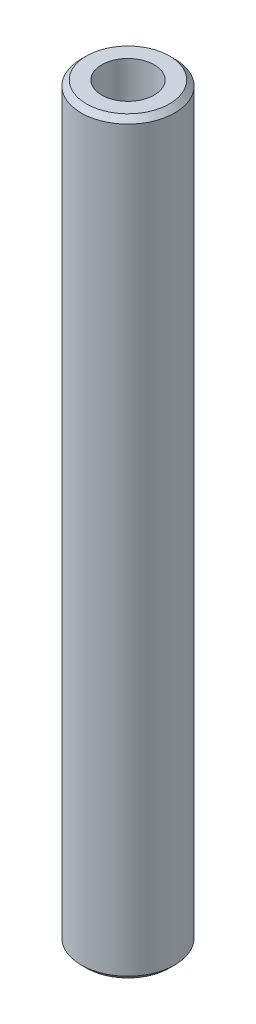
SolidWorks part; units mm, degrees
ref_plane "Front Plane" through (0, 0, 0) normal (0, 0, 1) x (1, 0, 0)
ref_plane "Top Plane" through (0, 0, 0) normal (0, 1, 0) x (1, 0, 0)
ref_plane "Right Plane" through (0, 0, 0) normal (1, 0, 0) x (0, 0, -1)
sketch "Sketch1" plane through (0, 0, 0) normal (0, 1, 0) x (1, 0, 0)
  circle A0 centre (0, 0) radius 37.5
  dimension "SHAFT_OD" = 75
extrude "Boss-Extrude1" add sketch "Sketch1" along normal blind 600
sketch "Sketch2" plane through (0, 0, 0) normal (0, 1, 0) x (1, 0, 0)
  circle A0 centre (0, 0) radius 21.0567
  dimension "BORE_D" = 42.1134
extrude "Cut-Extrude1" cut sketch "Sketch2" along normal through all
chamfer "Chamfer1" distance 4.2055 angle 45 2 edges at (0, 600, 37.5) (0, 0, 37.5)
